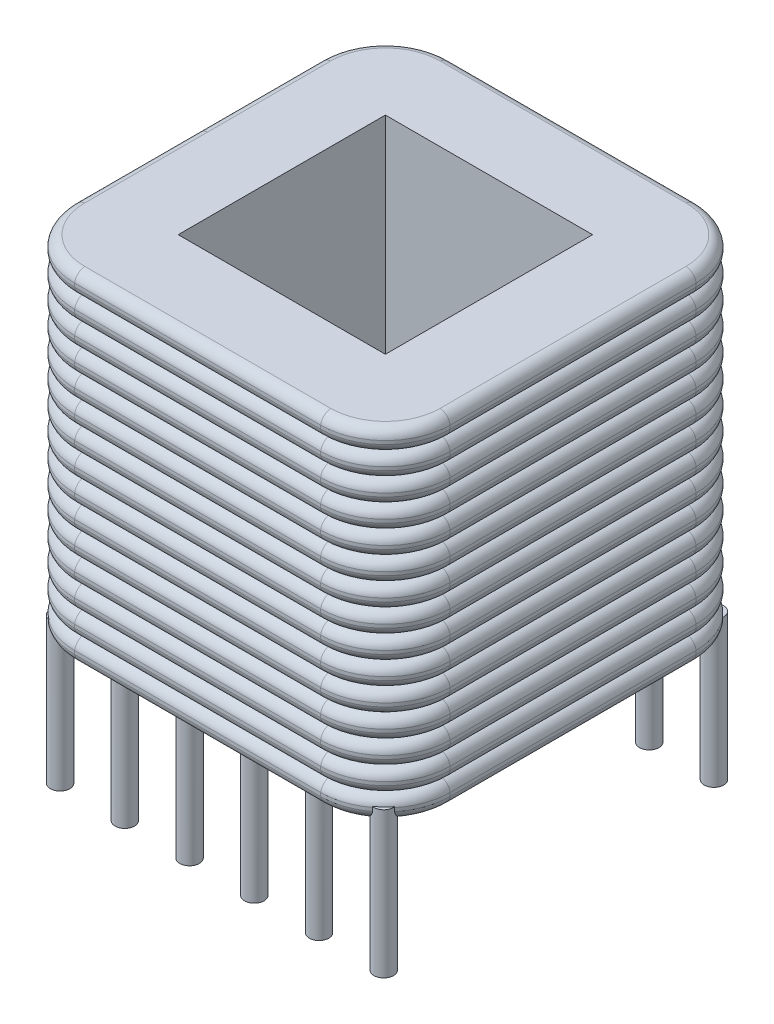
SolidWorks part; units mm, degrees
material "Copper"
ref_plane "Front Plane" through (0, 0, 0) normal (0, 0, 1) x (1, 0, 0)
ref_plane "Top Plane" through (0, 0, 0) normal (0, 1, 0) x (1, 0, 0)
ref_plane "Right Plane" through (0, 0, 0) normal (1, 0, 0) x (0, 0, -1)
sketch "Sketch2" plane through (0, 0, 0) normal (0, 1, 0) x (1, 0, 0)
  line L0 (-29, 19) -> (-29, -19)
  line L1 (-16, 16) -> (16, 16)
  line L2 (-16, 16) -> (-16, -16)
  line L3 (-16, -16) -> (16, -16)
  line L4 (16, 16) -> (16, -16)
  line L5 (-16, 16) -> (16, -16) construction
  line L6 (-16, -16) -> (16, 16) construction
  line L7 (-19, -29) -> (19, -29)
  line L8 (29, 19) -> (29, -19)
  line L9 (-19, 29) -> (19, 29)
  line L10 (29, 29) -> (29, -29) construction
  line L11 (-29, 29) -> (29, 29) construction
  line L12 (-29, -29) -> (29, -29) construction
  line L13 (-29, 29) -> (-29, -29) construction
  arc A0 (29, 19) -> (19, 29) centre (19, 19) ccw
  arc A1 (29, -19) -> (19, -29) centre (19, -19) cw
  arc A2 (-19, -29) -> (-29, -19) centre (-19, -19) cw
  arc A3 (-29, 19) -> (-19, 29) centre (-19, 19) cw
  point P0 (0, 0)
  dimension "D3" = 10
  dimension "D1" = 32
  dimension "D2" = 13
extrude "Boss-Extrude1" add sketch "Sketch2" along normal mid plane 53
sketch "Sketch3" plane through (0, 0, 0) normal (0, 0, 1) x (1, 0, 0)
  line L0 (-19, 26.5) -> (-29, 26.5) construction
  line L1 (-27.271, 26.51) -> (-27.271, 27.7106)
  line L2 (-27.271, 27.7106) -> (-29.6788, 27.7106)
  line L3 (-29.6788, 27.7106) -> (-29.6788, -28.0591)
  line L4 (-29.6788, -28.0591) -> (-27.271, -28.0591)
  line L5 (-27.271, -28.0591) -> (-27.271, -26.13)
  line L6 (-27.271, -22.62) -> (-27.271, -22.63)
  line L7 (-27.271, -19.11) -> (-27.271, -19.12)
  line L8 (-27.271, -15.6) -> (-27.271, -15.61)
  line L9 (-27.271, -12.09) -> (-27.271, -12.1)
  line L10 (-27.271, -8.58) -> (-27.271, -8.59)
  line L11 (-27.271, -5.07) -> (-27.271, -5.08)
  line L12 (-27.271, -1.56) -> (-27.271, -1.57)
  line L13 (-27.271, 1.95) -> (-27.271, 1.94)
  line L14 (-27.271, 5.46) -> (-27.271, 5.45)
  line L15 (-27.271, 8.97) -> (-27.271, 8.96)
  line L16 (-27.271, 12.48) -> (-27.271, 12.47)
  line L17 (-27.271, 15.99) -> (-27.271, 15.98)
  line L18 (-27.271, 19.5) -> (-27.271, 19.49)
  line L19 (-27.271, 23.01) -> (-27.271, 23)
  arc A0 (-27.271, 23.01) -> (-27.271, 26.51) centre (-27.271, 24.76) ccw construction
  arc A1 (-27.271, 23) -> (-27.271, 19.5) centre (-27.271, 21.25) ccw
  arc A2 (-27.271, 19.49) -> (-27.271, 15.99) centre (-27.271, 17.74) ccw
  arc A3 (-27.271, 15.98) -> (-27.271, 12.48) centre (-27.271, 14.23) ccw
  arc A4 (-27.271, 12.47) -> (-27.271, 8.97) centre (-27.271, 10.72) ccw
  arc A5 (-27.271, 8.96) -> (-27.271, 5.46) centre (-27.271, 7.21) ccw
  arc A6 (-27.271, 5.45) -> (-27.271, 1.95) centre (-27.271, 3.7) ccw
  arc A7 (-27.271, 1.94) -> (-27.271, -1.56) centre (-27.271, 0.19) ccw
  arc A8 (-27.271, -1.57) -> (-27.271, -5.07) centre (-27.271, -3.32) ccw
  arc A9 (-27.271, -5.08) -> (-27.271, -8.58) centre (-27.271, -6.83) ccw
  arc A10 (-27.271, -8.59) -> (-27.271, -12.09) centre (-27.271, -10.34) ccw
  arc A11 (-27.271, -12.1) -> (-27.271, -15.6) centre (-27.271, -13.85) ccw
  arc A12 (-27.271, -15.61) -> (-27.271, -19.11) centre (-27.271, -17.36) ccw
  arc A13 (-27.271, -19.12) -> (-27.271, -22.62) centre (-27.271, -20.87) ccw
  arc A14 (-27.271, -22.63) -> (-27.271, -26.13) centre (-27.271, -24.38) ccw
  arc A15 (-27.271, 26.51) -> (-27.271, 23.01) centre (-27.271, 24.76) ccw
  arc A16 (-27.271, 19.5) -> (-27.271, 23) centre (-27.271, 21.25) ccw construction
  arc A17 (-27.271, 15.99) -> (-27.271, 19.49) centre (-27.271, 17.74) ccw construction
  arc A18 (-27.271, 12.48) -> (-27.271, 15.98) centre (-27.271, 14.23) ccw construction
  arc A19 (-27.271, 8.97) -> (-27.271, 12.47) centre (-27.271, 10.72) ccw construction
  arc A20 (-27.271, 5.46) -> (-27.271, 8.96) centre (-27.271, 7.21) ccw construction
  arc A21 (-27.271, 1.95) -> (-27.271, 5.45) centre (-27.271, 3.7) ccw construction
  arc A22 (-27.271, -1.56) -> (-27.271, 1.94) centre (-27.271, 0.19) ccw construction
  arc A23 (-27.271, -5.07) -> (-27.271, -1.57) centre (-27.271, -3.32) ccw construction
  arc A24 (-27.271, -8.58) -> (-27.271, -5.08) centre (-27.271, -6.83) ccw construction
  arc A25 (-27.271, -12.09) -> (-27.271, -8.59) centre (-27.271, -10.34) ccw construction
  arc A26 (-27.271, -15.6) -> (-27.271, -12.1) centre (-27.271, -13.85) ccw construction
  arc A27 (-27.271, -19.11) -> (-27.271, -15.61) centre (-27.271, -17.36) ccw construction
  arc A28 (-27.271, -22.62) -> (-27.271, -19.12) centre (-27.271, -20.87) ccw construction
  arc A29 (-27.271, -26.13) -> (-27.271, -22.63) centre (-27.271, -24.38) ccw construction
  dimension "D1" = 1.74
  dimension "D2" = 3.5
  dimension "D3" = 15
sketch "Sketch4" plane through (0, 26.5, 0) normal (0, 1, 0) x (1, 0, 0)
  line L4 (19, 29) -> (-19, 29)
  line L5 (-29, 19) -> (-29, -19)
  line L6 (-19, -29) -> (19, -29)
  line L7 (29, -19) -> (29, 19)
  line L8 (19, 29) -> (-19, 29)
  line L9 (-29, 19) -> (-29, -19)
  line L10 (-19, -29) -> (19, -29)
  line L11 (29, -19) -> (29, 19)
  arc A4 (29, 19) -> (19, 29) centre (19, 19) ccw
  arc A5 (-19, 29) -> (-29, 19) centre (-19, 19) ccw
  arc A6 (-29, -19) -> (-19, -29) centre (-19, -19) ccw
  arc A7 (19, -29) -> (29, -19) centre (19, -19) ccw
  arc A8 (29, 19) -> (19, 29) centre (19, 19) ccw
  arc A9 (-19, 29) -> (-29, 19) centre (-19, 19) ccw
  arc A10 (-29, -19) -> (-19, -29) centre (-19, -19) ccw
  arc A11 (19, -29) -> (29, -19) centre (19, -19) ccw
  dimension "D1" = 0
sweep "Cut-Sweep1" cut profiles "Sketch3" path "Sketch4"
sketch "Sketch5" plane through (0, -26.5, 0) normal (0, -1, 0) x (1, 0, 0)
  circle A0 centre (-24.75, 25.5) radius 1.5
  arc A1 (-26.25, 25.5) -> (-23.25, 25.5) centre (-24.75, 25.5) ccw construction
  circle A2 centre (-14.75, 25.5) radius 1.5
  circle A3 centre (-4.75, 25.5) radius 1.5
  circle A4 centre (5.25, 25.5) radius 1.5
  circle A5 centre (15.25, 25.5) radius 1.5
  circle A6 centre (25.25, 25.5) radius 1.5
  circle A7 centre (-14.75, -25.5) radius 1.5
  circle A8 centre (-4.75, -25.5) radius 1.5
  circle A9 centre (5.25, -25.5) radius 1.5
  circle A10 centre (15.25, -25.5) radius 1.5
  circle A11 centre (25.25, -25.5) radius 1.5
  circle A12 centre (-24.75, -25.5) radius 1.5
  dimension "D1" = 6
  dimension "D3" = 3
  dimension "D2" = 2
extrude "Boss-Extrude2" add sketch "Sketch5" along normal blind 20 and the other way blind 2.5
